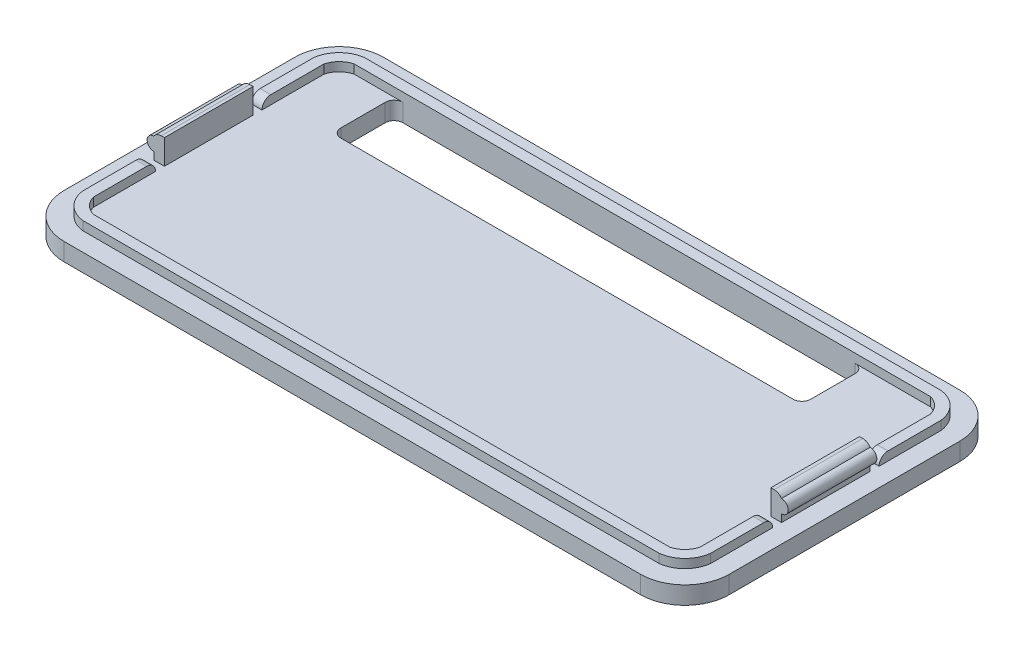
SolidWorks part; units mm, degrees
ref_plane "前视基准面" through (0, 0, 0) normal (0, 0, 1) x (1, 0, 0)
ref_plane "上视基准面" through (0, 0, 0) normal (0, 1, 0) x (1, 0, 0)
ref_plane "右视基准面" through (0, 0, 0) normal (1, 0, 0) x (0, 0, -1)
sketch "zero" plane through (0, 0, 0) normal (0, 1, 0) x (1, 0, 0)
  line L1 (-29.5, 15) -> (29.5, 15)
  line L2 (-32.5, 12) -> (-32.5, -12)
  line L3 (-29.5, -15) -> (29.5, -15)
  line L4 (32.5, 12) -> (32.5, -12)
  line L5 (-32.5, 15) -> (32.5, -15) construction
  line L6 (-32.5, -15) -> (32.5, 15) construction
  line L7 (-25.7, -15) -> (-14.5, -15)
  line L8 (-25.7, -15) -> (-25.7, -9.6569)
  line L9 (-25.7, -9.6569) -> (-14.5, -9.6569)
  line L10 (-14.5, -15) -> (-14.5, -9.6569)
  line L11 (5.2, -15) -> (12.7, -15)
  line L12 (5.2, -15) -> (5.2, -11)
  line L13 (5.2, -11) -> (12.7, -11)
  line L14 (12.7, -15) -> (12.7, -11)
  line L15 (17.8, -15) -> (25.3, -15)
  line L16 (17.8, -15) -> (17.8, -11)
  line L17 (17.8, -11) -> (25.3, -11)
  line L18 (25.3, -15) -> (25.3, -11)
  line L19 (-32.5, 7.7) -> (-19.5, 7.7)
  line L20 (-32.5, 7.7) -> (-32.5, -4.3)
  line L21 (-32.5, -4.3) -> (-19.5, -4.3)
  line L22 (-19.5, 7.7) -> (-19.5, -4.3)
  line L23 (-25.5, 14) -> (25.5, 14)
  line L24 (-25.5, 14) -> (-25.5, 8.8)
  line L25 (-25.5, 8.8) -> (25.5, 8.8)
  line L26 (25.5, 14) -> (25.5, 8.8)
  line L27 (-19.5, 7.2329) -> (-35.5, 7.2329)
  line L28 (-19.5, 7.2329) -> (-19.5, -3.7671)
  line L29 (-19.5, -3.7671) -> (-35.5, -3.7671)
  line L30 (-35.5, 7.2329) -> (-35.5, -3.7671)
  arc A0 (29.5, -15) -> (32.5, -12) centre (29.5, -12) ccw
  arc A1 (29.5, 15) -> (32.5, 12) centre (29.5, 12) cw
  arc A2 (-32.5, -12) -> (-29.5, -15) centre (-29.5, -12) ccw
  arc A3 (-29.5, 15) -> (-32.5, 12) centre (-29.5, 12) ccw
  circle A4 centre (-29, 11.4) radius 3
  circle A5 centre (-29, -11.5) radius 3
  circle A6 centre (29, 11.4) radius 3
  circle A7 centre (29, -11.5) radius 3
  circle A8 centre (-29, 11.4) radius 1.375
  circle A9 centre (-29, -11.5) radius 1.375
  circle A10 centre (29, -11.5) radius 1.375
  circle A11 centre (29, 11.4) radius 1.375
  point P0 (0, 0)
  dimension "D3" = 3
  dimension "D4" = 6
  dimension "D9" = 2.75
  dimension "D1" = 65
  dimension "D2" = 30
  dimension "D5" = 3.6
  dimension "D6" = 3.5
  dimension "D7" = 3.5
  dimension "D8" = 3.5
  dimension "D10" = 12
  dimension "D11" = 7.3
  dimension "D12" = 13
  dimension "D13" = 11.2
  dimension "D14" = 6.8
  dimension "D15" = 19.7
  dimension "D16" = 7.5
  dimension "D17" = 7.5
  dimension "D18" = 5.1
  dimension "D19" = 4
  dimension "D20" = 5.2
  dimension "D21" = 7
  dimension "D22" = 7
  dimension "D23" = 1
  dimension "D24" = 11
  dimension "D25" = 16
sketch "sugar" plane through (0, 0, 0) normal (0, 1, 0) x (1, 0, 0)
  line L1 (-29.5, 15) -> (29.5, 15)
  line L2 (-32.5, 12) -> (-32.5, -12)
  line L3 (-29.5, -15) -> (29.5, -15)
  line L4 (32.5, 12) -> (32.5, -12)
  line L5 (-32.5, 15) -> (32.5, -15) construction
  line L6 (-32.5, -15) -> (32.5, 15) construction
  line L7 (23.5, -11.5) -> (19.5, -11.5)
  line L8 (23.5, -11.5) -> (23.5, -13.9082)
  line L9 (23.5, -13.9082) -> (19.5, -13.9082)
  line L10 (19.5, -11.5) -> (19.5, -13.9082)
  line L11 (16, -11.0071) -> (8.5, -11.0071)
  line L12 (16, -11.0071) -> (16, -15)
  line L13 (16, -15) -> (8.5, -15)
  line L14 (8.5, -11.0071) -> (8.5, -15)
  line L15 (20.5, -13.9082) -> (22.5, -13.9082)
  line L16 (20.5, -13.9082) -> (20.5, -14.8173)
  line L17 (20.5, -14.8173) -> (22.5, -14.8173)
  line L18 (22.5, -13.9082) -> (22.5, -14.8173)
  arc A0 (29.5, 15) -> (32.5, 12) centre (29.5, 12) cw
  arc A1 (29.5, -15) -> (32.5, -12) centre (29.5, -12) ccw
  arc A2 (-32.5, -12) -> (-29.5, -15) centre (-29.5, -12) ccw
  arc A3 (-29.5, 15) -> (-32.5, 12) centre (-29.5, 12) ccw
  circle A4 centre (-29, 11.4) radius 3
  circle A5 centre (-29, 11.4) radius 1.375
  circle A6 centre (-29, -11.5) radius 3
  circle A7 centre (-29, -11.5) radius 1.375
  circle A8 centre (29, 11.4) radius 3
  circle A9 centre (29, 11.4) radius 1.375
  circle A10 centre (29, -11.5) radius 3
  circle A11 centre (29, -11.5) radius 1.375
  dimension "D3" = 3
  dimension "D1" = 65
  dimension "D2" = 30
  dimension "D4" = 9
  dimension "D5" = 4
  dimension "D6" = 3.5
  dimension "D7" = 7.5
  dimension "D8" = 2
  dimension "D9" = 1
sketch "case" plane through (0, 0, 0) normal (0, 1, 0) x (1, 0, 0)
  line L1 (-34.0422, 18) -> (30.9578, 18)
  line L2 (-39.0422, 13) -> (-39.0422, -13)
  line L3 (-34.0422, -18) -> (30.9578, -18)
  line L4 (35.9578, 13) -> (35.9578, -13)
  line L5 (-39.0422, 18) -> (35.9578, -18) construction
  line L6 (-39.0422, -18) -> (35.9578, 18) construction
  arc A0 (-39.0422, -13) -> (-34.0422, -18) centre (-34.0422, -13) ccw
  arc A1 (30.9578, -18) -> (35.9578, -13) centre (30.9578, -13) ccw
  arc A2 (30.9578, 18) -> (35.9578, 13) centre (30.9578, 13) cw
  arc A3 (-34.0422, 18) -> (-39.0422, 13) centre (-34.0422, 13) ccw
  point P0 (-1.5422, 0)
  point P3 (-1.5422, 0)
  dimension "D3" = 5
  dimension "D1" = 75
  dimension "D2" = 36
extrude "凸台-拉伸2" add sketch "case" along normal blind 2
sketch "草图2" plane through (0, 0, 0) normal (0, 1, 0) x (1, 0, 0)
  line L4 (-34.0422, -14.7) -> (30.9578, -14.7)
  line L5 (32.6578, -13) -> (32.6578, 13)
  line L6 (30.9578, 14.7) -> (-34.0422, 14.7)
  line L7 (-35.7422, 13) -> (-35.7422, -13)
  line L12 (33.8578, -13) -> (33.8578, 13)
  line L13 (30.9578, 15.9) -> (-34.0422, 15.9)
  line L14 (-36.9422, 13) -> (-36.9422, -13)
  line L15 (-34.0422, -15.9) -> (30.9578, -15.9)
  arc A4 (30.9578, -14.7) -> (32.6578, -13) centre (30.339, -12.3812) ccw
  arc A5 (32.6578, 13) -> (30.9578, 14.7) centre (30.339, 12.3812) ccw
  arc A6 (-34.0422, 14.7) -> (-35.7422, 13) centre (-33.4234, 12.3812) ccw
  arc A7 (-35.7422, -13) -> (-34.0422, -14.7) centre (-33.4234, -12.3812) ccw
  arc A12 (30.9578, -15.9) -> (33.8578, -13) centre (30.5796, -12.6217) ccw
  arc A13 (33.8578, 13) -> (30.9578, 15.9) centre (30.5796, 12.6217) ccw
  arc A14 (-34.0422, 15.9) -> (-36.9422, 13) centre (-33.6639, 12.6217) ccw
  arc A15 (-36.9422, -13) -> (-34.0422, -15.9) centre (-33.6639, -12.6217) ccw
ref_plane "基准面1" through (0, 2, 0) normal (0, 1, 0) x (1, 0, 0)
sketch "草图3" plane through (0, 2, 0) normal (0, 1, 0) x (1, 0, 0)
  line L4 (-34.0422, -14.7) -> (30.9578, -14.7)
  line L5 (32.6578, -13) -> (32.6578, 13)
  line L6 (30.9578, 14.7) -> (-34.0422, 14.7)
  line L7 (-35.7422, 13) -> (-35.7422, -13)
  line L8 (-34.0422, -14.7) -> (30.9578, -14.7)
  line L9 (32.6578, -13) -> (32.6578, 13)
  line L10 (30.9578, 14.7) -> (-34.0422, 14.7)
  line L11 (-35.7422, 13) -> (-35.7422, -13)
  line L12 (-36.9422, 13) -> (-36.9422, -13)
  line L13 (-34.0422, -15.9) -> (30.9578, -15.9)
  line L14 (33.8578, -13) -> (33.8578, 13)
  line L15 (30.9578, 15.9) -> (-34.0422, 15.9)
  line L16 (-36.9422, 13) -> (-36.9422, -13)
  line L17 (-34.0422, -15.9) -> (30.9578, -15.9)
  line L18 (33.8578, -13) -> (33.8578, 13)
  line L19 (30.9578, 15.9) -> (-34.0422, 15.9)
  arc A4 (30.9578, -14.7) -> (32.6578, -13) centre (30.339, -12.3812) ccw
  arc A5 (32.6578, 13) -> (30.9578, 14.7) centre (30.339, 12.3812) ccw
  arc A6 (-34.0422, 14.7) -> (-35.7422, 13) centre (-33.4234, 12.3812) ccw
  arc A7 (-35.7422, -13) -> (-34.0422, -14.7) centre (-33.4234, -12.3812) ccw
  arc A8 (30.9578, -14.7) -> (32.6578, -13) centre (30.339, -12.3812) ccw
  arc A9 (32.6578, 13) -> (30.9578, 14.7) centre (30.339, 12.3812) ccw
  arc A10 (-34.0422, 14.7) -> (-35.7422, 13) centre (-33.4234, 12.3812) ccw
  arc A11 (-35.7422, -13) -> (-34.0422, -14.7) centre (-33.4234, -12.3812) ccw
  arc A12 (-36.9422, -13) -> (-34.0422, -15.9) centre (-33.6639, -12.6217) ccw
  arc A13 (30.9578, -15.9) -> (33.8578, -13) centre (30.5796, -12.6217) ccw
  arc A14 (33.8578, 13) -> (30.9578, 15.9) centre (30.5796, 12.6217) ccw
  arc A15 (-34.0422, 15.9) -> (-36.9422, 13) centre (-33.6639, 12.6217) ccw
  arc A16 (-36.9422, -13) -> (-34.0422, -15.9) centre (-33.6639, -12.6217) ccw
  arc A17 (30.9578, -15.9) -> (33.8578, -13) centre (30.5796, -12.6217) ccw
  arc A18 (33.8578, 13) -> (30.9578, 15.9) centre (30.5796, 12.6217) ccw
  arc A19 (-34.0422, 15.9) -> (-36.9422, 13) centre (-33.6639, 12.6217) ccw
  dimension "D1" = 0
  dimension "D2" = 0
extrude "凸台-拉伸4" add sketch "草图3" along normal blind 1
ref_plane "基准面3" through (33.8578, 0, 0) normal (1, 0, 0) x (0, 0, -1)
sketch "草图7" plane through (0, 2, 0) normal (0, 1, 0) x (1, 0, 0)
  line L0 (-36.9422, 13) -> (-36.9422, -13) construction
  line L1 (-36.9422, 5) -> (-35.7422, 5)
  line L2 (-36.9422, 5) -> (-36.9422, -5)
  line L3 (-36.9422, -5) -> (-35.7422, -5)
  line L4 (-35.7422, 5) -> (-35.7422, -5)
  line L5 (-35.7422, 13) -> (-35.7422, -13) construction
  point P10 (-35.7422, 0)
  dimension "D1" = 5
  dimension "D2" = 10
extrude "凸台-拉伸8" add sketch "草图7" along normal blind 2.8
ref_plane "基准面5" through (0, 0, 5) normal (0, 0, 1) x (1, 0, 0)
sketch "草图8" plane through (0, 0, 5) normal (0, 0, 1) x (1, 0, 0)
  line L0 (-34.0422, 2) -> (-39.0422, 2) construction
  line L1 (-36.9422, 4.8) -> (-36.9422, 3) construction
  circle A0 centre (-36.9422, 3.6) radius 0.75
  dimension "D1" = 1.5
  dimension "D2" = 1.6
  dimension "D3" = 0
extrude "凸台-拉伸9" add sketch "草图8" against normal blind 10
fillet "圆角1" radius 1 1 edges at (-36.9422, 4.8, 0)
ref_plane "基准面7" through (-36.9422, 0, 0) normal (-1, 0, 0) x (0, 0, 1)
sketch "草图11" plane through (-36.9422, 0, 0) normal (-1, 0, 0) x (0, 0, 1)
  line L0 (-13, 2) -> (13, 2) construction
  line L1 (5, 3) -> (6, 3)
  line L2 (5, 3) -> (5, 2)
  line L3 (5, 2) -> (6, 2)
  line L4 (6, 3) -> (6, 2)
  line L6 (-5, 3) -> (-6, 3)
  line L7 (-5, 3) -> (-5, 2)
  line L8 (-5, 2) -> (-6, 2)
  line L9 (-6, 3) -> (-6, 2)
  dimension "D1" = 1
  dimension "D2" = 1
extrude "切除-拉伸1" cut sketch "草图11" against normal blind 1.2
fillet "圆角2" radius 1 2 edges at (-36.3422, 3, 6) (-36.3422, 3, -6)
ref_plane "基准面8" through (0, 0, 0) normal (0, -1, 0) x (-1, 0, 0)
sketch "草图12" plane through (0, 0, 0) normal (0, -1, 0) x (-1, 0, 0)
  line L76 (34.0422, -18) -> (-30.9578, -18) construction
  line L78 (39.0422, 13) -> (39.0422, -13) construction
  line B0 (-8.1993, 1.426) -> (-9.0198, 1.899)
  line B1 (-9.0198, 1.899) -> (-13.2767, 4.3551)
  line B2 (-13.2767, 4.3551) -> (-14.0973, 4.8339)
  line B3 (-15.8183, 4.8339) -> (-16.6389, 4.3551)
  line B4 (-16.6389, 4.3551) -> (-20.8958, 1.899)
  line B5 (-20.8958, 1.899) -> (-21.7165, 1.426)
  line B6 (-22.577, -0.0613) -> (-22.577, -6.8769)
  line B7 (-21.7165, -8.3643) -> (-20.8958, -8.8373)
  line B8 (-20.8958, -8.8373) -> (-16.6389, -11.2934)
  line B9 (-16.6389, -11.2934) -> (-15.8183, -11.772)
  line B10 (-14.0973, -11.772) -> (-13.2767, -11.2934)
  line B11 (-13.2767, -11.2934) -> (-9.0198, -8.8373)
  line B12 (-9.0198, -8.8373) -> (-8.1993, -8.3643)
  line B13 (-7.3388, -6.8769) -> (-7.3388, -0.0613)
  line B14 (-20.6223, 0.7479) -> (-15.3568, 3.791)
  line B15 (-14.5532, 3.791) -> (-9.3162, 0.7422)
  line B16 (-9.3105, 0.0413) -> (-14.3993, -3.0018)
  line B17 (-12.8208, -8.1591) -> (-13.4135, -8.4896)
  line B18 (-13.4705, -8.5865) -> (-13.4705, -10.2961)
  line B19 (-13.5274, -10.393) -> (-14.633, -11.0198)
  line B20 (-14.7983, -10.9229) -> (-14.7983, -5.646)
  line B21 (-14.7413, -5.5491) -> (-12.8607, -4.4835)
  line B22 (-8.9173, -7.8058) -> (-10.0114, -8.4269)
  line B23 (-10.1767, -8.3301) -> (-10.1767, -5.8169)
  line B24 (-10.1197, -5.7201) -> (-9.0256, -5.1046)
  line B25 (-8.8603, -5.2015) -> (-8.8603, -7.7089)
  line B26 (-12.8893, -7.1447) -> (-13.4135, -7.4069)
  line B27 (-13.4705, -7.2872) -> (-13.4705, -5.9423)
  line B28 (-13.4135, -5.8455) -> (-12.9234, -5.5719)
  line B29 (-3.344, -0.54) -> (-5.2189, -0.54)
  line B30 (-5.2189, -0.54) -> (-5.2189, -7.1048)
  line B31 (-5.2189, -7.1048) -> (-4.3868, -7.1048)
  line B32 (-4.3868, -7.1048) -> (-4.3868, -4.5005)
  line B33 (-4.3868, -4.5005) -> (-3.2984, -4.5005)
  line B34 (-3.4066, -3.8281) -> (-4.3868, -3.8281)
  line B35 (-4.3868, -3.8281) -> (-4.3868, -1.2124)
  line B36 (-4.3868, -1.2124) -> (-3.4408, -1.2124)
  line B37 (0.1948, -2.2382) -> (0.1948, -7.1048)
  line B38 (0.1948, -7.1048) -> (1.0098, -7.1048)
  line B39 (1.0098, -7.1048) -> (1.0098, -2.2382)
  line B40 (1.0098, -2.2382) -> (0.1948, -2.2382)
  line B41 (5.7169, -3.3153) -> (4.8849, -2.9847)
  line B42 (6.0417, -2.1983) -> (6.8396, -1.1953)
  line B43 (3.6084, -4.1586) -> (4.4575, -4.5177)
  line B44 (2.9074, -5.1673) -> (2.0014, -6.2729)
  line B45 (10.8229, -2.0102) -> (10.8229, -5.3497)
  line B46 (9.3811, -4.9621) -> (9.3811, -2.0102)
  line B47 (9.3811, -2.0102) -> (7.7912, -2.0102)
  line B48 (7.7912, -2.0102) -> (7.7912, -5.1616)
  line B49 (10.9711, -6.4039) -> (11.0052, -6.4039)
  line B50 (11.0052, -6.4039) -> (11.1193, -7.1048)
  line B51 (11.1193, -7.1048) -> (12.4185, -7.1048)
  line B52 (12.4185, -7.1048) -> (12.4185, -2.0102)
  line B53 (12.4185, -2.0102) -> (10.8229, -2.0102)
  line B54 (16.2708, -6.1019) -> (15.4673, -6.1019)
  line B55 (17.365, -3.1614) -> (18.1513, -3.1614)
  line B56 (18.1513, -3.1614) -> (18.1513, -2.0102)
  line B57 (18.1513, -2.0102) -> (16.2822, -2.0102)
  line B58 (14.0312, -5.0533) -> (14.0312, -5.0875)
  line B59 (13.9344, -6.9168) -> (13.9344, -6.9624)
  line B60 (15.4844, -7.3214) -> (15.9688, -7.3214)
  line B61 (18.6072, -2.5516) -> (19.1657, -3.6002)
  line B62 (21.411, -6.592) -> (21.4508, -6.592)
  line B63 (21.4508, -6.592) -> (21.5648, -7.1048)
  line B64 (21.5648, -7.1048) -> (22.8641, -7.1048)
  line B65 (22.8641, -7.1048) -> (22.8641, -4.2099)
  line B66 (21.2685, -4.7741) -> (21.2685, -5.589)
  line B67 (25.3545, -2.8935) -> (25.3203, -2.8935)
  line B68 (25.3203, -2.8935) -> (25.212, -2.0102)
  line B69 (25.212, -2.0102) -> (23.9127, -2.0102)
  line B70 (23.9127, -2.0102) -> (23.9127, -7.1048)
  line B71 (23.9127, -7.1048) -> (25.4969, -7.1048)
  line B72 (25.4969, -7.1048) -> (25.4969, -4.1928)
  line B73 (27.1552, -3.3608) -> (27.423, -1.9875)
  line B74 (-13.4135, -7.4069) -> (-13.4135, -8.4896)
  line B75 (-13.4705, -7.2872) -> (-13.4705, -8.5865)
  spline B76 degree 3 poles (-14.0973, 4.8339) (-14.3652, 4.982) (-14.6615, 5.0618) (-14.9578, 5.0618) knots 3 3 3 3 4 4 4 4
  spline B77 degree 3 poles (-14.9578, 5.0618) (-15.2541, 5.0618) (-15.5505, 4.982) (-15.8183, 4.8339) knots 4 4 4 4 5 5 5 5
  spline B78 degree 3 poles (-21.7165, 1.426) (-22.2464, 1.1183) (-22.577, 0.5485) (-22.577, -0.0613) knots 8 8 8 8 9 9 9 9
  spline B79 degree 3 poles (-22.577, -6.8769) (-22.577, -7.4923) (-22.2464, -8.0565) (-21.7165, -8.3643) knots 10 10 10 10 11 11 11 11
  spline B80 degree 3 poles (-15.8183, -11.772) (-15.5505, -11.9259) (-15.2541, -12) (-14.9578, -12) knots 14 14 14 14 15 15 15 15
  spline B81 degree 3 poles (-14.9578, -12) (-14.6615, -12) (-14.3652, -11.9259) (-14.0973, -11.772) knots 15 15 15 15 16 16 16 16
  spline B82 degree 3 poles (-8.1993, -8.3643) (-7.6636, -8.0565) (-7.3388, -7.4923) (-7.3388, -6.8769) knots 19 19 19 19 20 20 20 20
  spline B83 degree 3 poles (-7.3388, -0.0613) (-7.3388, 0.5485) (-7.6636, 1.1183) (-8.1993, 1.426) knots 21 21 21 21 22 22 22 22
  spline B84 degree 2 poles (-15.5106, -3.0018) (-20.6622, -0.0271) (-20.6736, -0.0214) knots 0 0 0 1 1 1
  spline B85 degree 3 poles (-20.6736, -0.0214) (-20.9414, 0.1723) (-20.9129, 0.5826) (-20.6223, 0.7479) knots 1 1 1 1 2 2 2 2
  spline B86 degree 3 poles (-15.3568, 3.791) (-15.1117, 3.9335) (-14.8039, 3.9335) (-14.5532, 3.791) knots 3 3 3 3 4 4 4 4
  spline B87 degree 3 poles (-9.3162, 0.7422) (-9.0484, 0.5883) (-9.0427, 0.2008) (-9.3105, 0.0413) knots 5 5 5 5 6 6 6 6
  spline B88 degree 3 poles (-14.3993, -3.0018) (-14.7413, -3.2013) (-15.1687, -3.2013) (-15.5106, -3.0018) knots 7 7 7 7 8 8 8 8
  spline B89 degree 3 poles (-13.4705, -10.2961) (-13.4705, -10.336) (-13.4876, -10.3702) (-13.5274, -10.393) knots 3 3 3 3 4 4 4 4
  spline B90 degree 3 poles (-14.633, -11.0198) (-14.7071, -11.0597) (-14.7983, -11.0084) (-14.7983, -10.9229) knots 5 5 5 5 6 6 6 6
  spline B91 degree 3 poles (-14.7983, -5.646) (-14.7983, -5.6061) (-14.7812, -5.5662) (-14.7413, -5.5491) knots 7 7 7 7 8 8 8 8
  spline B92 degree 3 poles (-12.8607, -4.4835) (-11.6412, -3.7939) (-10.6326, -3.6572) (-10.6326, -5.0249) knots 9 9 9 9 10 10 10 10
  spline B93 degree 3 poles (-10.6326, -5.0249) (-10.6326, -6.3412) (-11.6526, -7.498) (-12.8208, -8.1591) knots 10 10 10 10 11 11 11 11
  spline B94 degree 3 poles (-8.8603, -7.7089) (-8.8603, -7.7488) (-8.8831, -7.7887) (-8.9173, -7.8058) knots 0 0 0 0 1 1 1 1
  spline B95 degree 3 poles (-10.0114, -8.4269) (-10.0855, -8.4668) (-10.1767, -8.4155) (-10.1767, -8.3301) knots 2 2 2 2 3 3 3 3
  spline B96 degree 3 poles (-10.1767, -5.8169) (-10.1767, -5.7771) (-10.1539, -5.7429) (-10.1197, -5.7201) knots 4 4 4 4 5 5 5 5
  spline B97 degree 3 poles (-9.0256, -5.1046) (-8.9515, -5.0647) (-8.8603, -5.116) (-8.8603, -5.2015) knots 6 6 6 6 7 7 7 7
  spline B98 degree 3 poles (-9.5156, -3.4349) (-9.0768, -3.1842) (-8.7634, -3.2924) (-8.7634, -3.6914) (-8.7634, -4.0846) (-9.0768, -4.5461) (-9.5156, -4.7912) knots 2 2 2 2 3 3 3 4 4 4 4
  spline B99 degree 3 poles (-9.5156, -4.7912) (-9.9601, -5.0476) (-10.2735, -4.9394) (-10.2735, -4.5461) (-10.2735, -4.1415) (-9.9601, -3.6856) (-9.5156, -3.4349) knots 0 0 0 0 1 1 1 2 2 2 2
  spline B100 degree 3 poles (-11.9319, -5.76) (-11.9319, -6.3013) (-12.2395, -6.78) (-12.8893, -7.1447) knots 0 0 0 0 1 1 1 1
  spline B101 degree 3 poles (-13.4705, -5.9423) (-13.4705, -5.9024) (-13.4477, -5.8625) (-13.4135, -5.8455) knots 4 4 4 4 5 5 5 5
  spline B102 degree 3 poles (-12.9234, -5.5719) (-12.2852, -5.2072) (-11.9319, -5.2015) (-11.9319, -5.76) knots 6 6 6 6 7 7 7 7
  spline B103 degree 3 poles (-3.2984, -4.5005) (-1.868, -4.5005) (-0.8822, -3.8509) (-0.8822, -2.4661) knots 5 5 5 5 6 6 6 6
  spline B104 degree 3 poles (-0.8822, -2.4661) (-0.8822, -1.0301) (-1.868, -0.54) (-3.344, -0.54) knots 6 6 6 6 7 7 7 7
  spline B105 degree 3 poles (-3.4408, -1.2124) (-2.2897, -1.2124) (-1.7084, -1.5145) (-1.7084, -2.4661) knots 3 3 3 3 4 4 4 4
  spline B106 degree 3 poles (-1.7084, -2.4661) (-1.7084, -3.4064) (-2.2498, -3.8281) (-3.4066, -3.8281) knots 4 4 4 4 5 5 5 5
  spline B107 degree 3 poles (0.6052, -1.2352) (0.93, -1.2352) (1.1694, -1.013) (1.1694, -0.711) (1.1694, -0.3747) (0.93, -0.181) (0.6052, -0.181) knots 2 2 2 2 3 3 3 4 4 4 4
  spline B108 degree 3 poles (0.6052, -0.181) (0.2804, -0.181) (0.041, -0.3747) (0.041, -0.711) (0.041, -1.013) (0.2804, -1.2352) (0.6052, -1.2352) knots 0 0 0 0 1 1 1 2 2 2 2
  spline B109 degree 3 poles (4.8849, -2.9847) (4.2979, -2.7511) (3.8762, -2.6086) (3.8762, -2.2382) knots 1 1 1 1 2 2 2 2
  spline B110 degree 3 poles (3.8762, -2.2382) (3.8762, -1.8849) (4.1783, -1.6854) (4.674, -1.6854) knots 2 2 2 2 3 3 3 3
  spline B111 degree 3 poles (4.674, -1.6854) (5.1926, -1.6854) (5.6029, -1.8621) (6.0417, -2.1983) knots 3 3 3 3 4 4 4 4
  spline B112 degree 3 poles (6.8396, -1.1953) (6.2583, -0.6084) (5.4433, -0.3121) (4.674, -0.3121) knots 5 5 5 5 6 6 6 6
  spline B113 degree 3 poles (4.674, -0.3121) (3.2551, -0.3121) (2.2521, -1.2124) (2.2521, -2.3294) knots 6 6 6 6 7 7 7 7
  spline B114 degree 3 poles (2.2521, -2.3294) (2.2521, -3.2981) (2.9074, -3.8794) (3.6084, -4.1586) knots 7 7 7 7 8 8 8 8
  spline B115 degree 3 poles (4.4575, -4.5177) (5.0274, -4.757) (5.3978, -4.8824) (5.3978, -5.2699) knots 9 9 9 9 10 10 10 10
  spline B116 degree 3 poles (5.3978, -5.2699) (5.3978, -5.6289) (5.1185, -5.8511) (4.5259, -5.8511) knots 10 10 10 10 11 11 11 11
  spline B117 degree 3 poles (4.5259, -5.8511) (4.0016, -5.8511) (3.3804, -5.5719) (2.9074, -5.1673) knots 11 11 11 11 12 12 12 12
  spline B118 degree 3 poles (2.0014, -6.2729) (2.6909, -6.9054) (3.6254, -7.2302) (4.4916, -7.2302) knots 13 13 13 13 14 14 14 14
  spline B119 degree 3 poles (4.4916, -7.2302) (6.1044, -7.2302) (7.0389, -6.2557) (7.0389, -5.1445) knots 14 14 14 14 15 15 15 15
  spline B120 degree 3 poles (7.0389, -5.1445) (7.0389, -4.2042) (6.5432, -3.6458) (5.7169, -3.3153) knots 15 15 15 15 16 16 16 16
  spline B121 degree 3 poles (10.8229, -5.3497) (10.5551, -5.7258) (10.3328, -5.8682) (9.9738, -5.8682) knots 1 1 1 1 2 2 2 2
  spline B122 degree 3 poles (9.9738, -5.8682) (9.5692, -5.8682) (9.3811, -5.6688) (9.3811, -4.9621) knots 2 2 2 2 3 3 3 3
  spline B123 degree 3 poles (7.7912, -5.1616) (7.7912, -6.4324) (8.2642, -7.2302) (9.3754, -7.2302) knots 6 6 6 6 7 7 7 7
  spline B124 degree 3 poles (9.3754, -7.2302) (10.0706, -7.2302) (10.5494, -6.9054) (10.9711, -6.4039) knots 7 7 7 7 8 8 8 8
  spline B125 degree 3 poles (15.4673, -6.1019) (14.9202, -6.1019) (14.7151, -5.9936) (14.7151, -5.76) knots 1 1 1 1 2 2 2 2
  spline B126 degree 3 poles (14.7151, -5.76) (14.7151, -5.589) (14.7549, -5.5092) (14.8746, -5.4009) knots 2 2 2 2 3 3 3 3
  spline B127 degree 3 poles (14.8746, -5.4009) (15.0969, -5.4636) (15.302, -5.4921) (15.473, -5.4921) knots 3 3 3 3 4 4 4 4
  spline B128 degree 3 poles (15.473, -5.4921) (16.6013, -5.4921) (17.5074, -4.9735) (17.5074, -3.7825) knots 4 4 4 4 5 5 5 5
  spline B129 degree 3 poles (17.5074, -3.7825) (17.5074, -3.5375) (17.4447, -3.3038) (17.365, -3.1614) knots 5 5 5 5 6 6 6 6
  spline B130 degree 3 poles (16.2822, -2.0102) (16.0485, -1.9248) (15.7693, -1.8849) (15.473, -1.8849) knots 9 9 9 9 10 10 10 10
  spline B131 degree 3 poles (15.473, -1.8849) (14.3732, -1.8849) (13.3417, -2.4889) (13.3417, -3.7369) knots 10 10 10 10 11 11 11 11
  spline B132 degree 3 poles (13.3417, -3.7369) (13.3417, -4.3296) (13.6722, -4.8026) (14.0312, -5.0533) knots 11 11 11 11 12 12 12 12
  spline B133 degree 3 poles (14.0312, -5.0875) (13.7007, -5.3212) (13.467, -5.6802) (13.467, -6.0392) knots 13 13 13 13 14 14 14 14
  spline B134 degree 3 poles (13.467, -6.0392) (13.467, -6.4666) (13.6665, -6.7344) (13.9344, -6.9168) knots 14 14 14 14 15 15 15 15
  spline B135 degree 3 poles (13.9344, -6.9624) (13.4613, -7.2017) (13.2106, -7.5436) (13.2106, -7.9653) knots 16 16 16 16 17 17 17 17
  spline B136 degree 3 poles (13.2106, -7.9653) (13.2106, -8.8771) (14.1737, -9.2475) (15.3476, -9.2475) knots 17 17 17 17 18 18 18 18
  spline B137 degree 3 poles (15.3476, -9.2475) (17.1199, -9.2475) (18.2312, -8.4839) (18.2312, -7.4069) knots 18 18 18 18 19 19 19 19
  spline B138 degree 3 poles (18.2312, -7.4069) (18.2312, -6.4837) (17.5245, -6.1019) (16.2708, -6.1019) knots 19 19 19 19 20 20 20 20
  spline B139 degree 3 poles (15.473, -4.5347) (15.1083, -4.5347) (14.8291, -4.2669) (14.8291, -3.7369) (14.8291, -3.2184) (15.1083, -2.9505) (15.473, -2.9505) knots 2 2 2 2 3 3 3 4 4 4 4
  spline B140 degree 3 poles (15.473, -2.9505) (15.8491, -2.9505) (16.1169, -3.2184) (16.1169, -3.7369) (16.1169, -4.2669) (15.8491, -4.5347) (15.473, -4.5347) knots 0 0 0 0 1 1 1 2 2 2 2
  spline B141 degree 3 poles (15.5983, -8.2503) (14.943, -8.2503) (14.5156, -8.0736) (14.5156, -7.7146) knots 0 0 0 0 1 1 1 1
  spline B142 degree 3 poles (14.5156, -7.7146) (14.5156, -7.5436) (14.5953, -7.4012) (14.7549, -7.2587) knots 1 1 1 1 2 2 2 2
  spline B143 degree 3 poles (14.7549, -7.2587) (14.9202, -7.3043) (15.114, -7.3214) (15.4844, -7.3214) knots 2 2 2 2 3 3 3 3
  spline B144 degree 3 poles (15.9688, -7.3214) (16.4417, -7.3214) (16.7096, -7.3841) (16.7096, -7.6861) knots 4 4 4 4 5 5 5 5
  spline B145 degree 3 poles (16.7096, -7.6861) (16.7096, -8.0109) (16.2537, -8.2503) (15.5983, -8.2503) knots 5 5 5 5 6 6 6 6
  spline B146 degree 3 poles (20.8013, -1.8849) (20.0091, -1.8849) (19.2797, -2.1527) (18.6072, -2.5516) knots 0 0 0 0 1 1 1 1
  spline B147 degree 3 poles (19.1657, -3.6002) (19.6729, -3.3153) (20.0946, -3.1557) (20.4992, -3.1557) knots 2 2 2 2 3 3 3 3
  spline B148 degree 3 poles (20.4992, -3.1557) (21.0177, -3.1557) (21.2344, -3.395) (21.2685, -3.8053) knots 3 3 3 3 4 4 4 4
  spline B149 degree 3 poles (21.2685, -3.8053) (19.2797, -4.0219) (18.4362, -4.6031) (18.4362, -5.6802) knots 4 4 4 4 5 5 5 5
  spline B150 degree 3 poles (18.4362, -5.6802) (18.4362, -6.5293) (19.0118, -7.2302) (19.9522, -7.2302) knots 5 5 5 5 6 6 6 6
  spline B151 degree 3 poles (19.9522, -7.2302) (20.5163, -7.2302) (20.9893, -6.9681) (21.411, -6.592) knots 6 6 6 6 7 7 7 7
  spline B152 degree 3 poles (22.8641, -4.2099) (22.8641, -2.6143) (22.1176, -1.8849) (20.8013, -1.8849) knots 11 11 11 11 12 12 12 12
  spline B153 degree 3 poles (21.2685, -5.589) (21.0349, -5.8398) (20.824, -5.9936) (20.4992, -5.9936) knots 0 0 0 0 1 1 1 1
  spline B154 degree 3 poles (20.4992, -5.9936) (20.1686, -5.9936) (19.9522, -5.8511) (19.9522, -5.5548) knots 1 1 1 1 2 2 2 2
  spline B155 degree 3 poles (19.9522, -5.5548) (19.9522, -5.1958) (20.277, -4.9109) (21.2685, -4.7741) knots 2 2 2 2 3 3 3 3
  spline B156 degree 3 poles (26.8076, -1.8849) (26.2947, -1.8849) (25.7305, -2.2154) (25.3545, -2.8935) knots 0 0 0 0 1 1 1 1
  spline B157 degree 3 poles (25.4969, -4.1928) (25.7648, -3.5204) (26.2207, -3.2811) (26.5967, -3.2811) knots 7 7 7 7 8 8 8 8
  spline B158 degree 3 poles (26.5967, -3.2811) (26.8247, -3.2811) (26.9729, -3.3153) (27.1552, -3.3608) knots 8 8 8 8 9 9 9 9
  spline B159 degree 3 poles (27.423, -1.9875) (27.2806, -1.9248) (27.1096, -1.8849) (26.8076, -1.8849) knots 10 10 10 10 11 11 11 11
  dimension "D1" = 6
  dimension "D2" = 54
sketch_block_instance "块1-1"
sketch_block "块1"
extrude "切除-拉伸2" cut sketch "草图12" against normal blind 0.5
sketch "草图13" plane through (0, 0, 0) normal (0, 1, 0) x (1, 0, 0)
  line L0 (30.9578, 18) -> (-34.0422, 18) construction
  line L1 (-29.5422, 14.7) -> (23.4578, 14.7)
  line L2 (-29.5422, 14.7) -> (-29.5422, 7.7)
  line L3 (-29.5422, 7.7) -> (23.4578, 7.7)
  line L4 (23.4578, 14.7) -> (23.4578, 7.7)
  line L6 (-39.0422, 13) -> (-39.0422, -13) construction
  dimension "D1" = 7
  dimension "D2" = 53
  dimension "D3" = 3.3
  dimension "D4" = 9.5
extrude "切除-拉伸3" cut sketch "草图13" along normal blind 2
fillet "圆角3" radius 1 4 edges at (-29.5422, 1, -14.7) (-29.5422, 1, -7.7) (23.4578, 1, -14.7) (23.4578, 1, -7.7)
sketch "草图14" plane through (0, 3, 0) normal (0, 1, 0) x (1, 0, 0)
  line L0 (33.8578, -13) -> (33.8578, 13) construction
  line L1 (33.8578, 5) -> (32.6578, 5)
  line L2 (33.8578, 5) -> (33.8578, -5)
  line L3 (33.8578, -5) -> (32.6578, -5)
  line L4 (32.6578, 5) -> (32.6578, -5)
  line L5 (32.6578, -13) -> (32.6578, 13) construction
  line L6 (35.9578, -13) -> (35.9578, 13) construction
  point P10 (33.8578, 0)
  point P11 (35.9578, 0)
  dimension "D1" = 10
extrude "凸台-拉伸10" add sketch "草图14" along normal blind 1.8
sketch "草图15" plane through (0, 0, -5) normal (0, 0, -1) x (-1, 0, 0)
  line L0 (-30.9578, 2) -> (-35.9578, 2) construction
  line L1 (-33.8578, 4.8) -> (-33.8578, 3) construction
  circle A0 centre (-33.8578, 3.6) radius 0.75
  dimension "D1" = 1.5
  dimension "D2" = 1.6
  dimension "D3" = 0
extrude "凸台-拉伸11" add sketch "草图15" against normal blind 10 contours A0
fillet "圆角4" radius 1 1 edges at (33.8578, 4.8, 0)
sketch "草图16" plane through (0, 3, 0) normal (0, 1, 0) x (1, 0, 0)
  line L0 (33.8578, -13) -> (33.8578, -5) construction
  line L1 (32.6578, -5) -> (33.8578, -5)
  line L2 (32.6578, -5) -> (32.6578, -6)
  line L3 (32.6578, -6) -> (33.8578, -6)
  line L4 (33.8578, -5) -> (33.8578, -6)
  line L5 (33.8578, 5) -> (33.8578, 13) construction
  line L6 (32.6578, 5) -> (33.8578, 5)
  line L7 (32.6578, 5) -> (32.6578, 6)
  line L8 (32.6578, 6) -> (33.8578, 6)
  line L9 (33.8578, 5) -> (33.8578, 6)
  dimension "D1" = 1
  dimension "D2" = 1
extrude "切除-拉伸4" cut sketch "草图16" against normal blind 1
fillet "圆角5" radius 1 2 edges at (33.2578, 3, 6) (33.2578, 3, -6)
